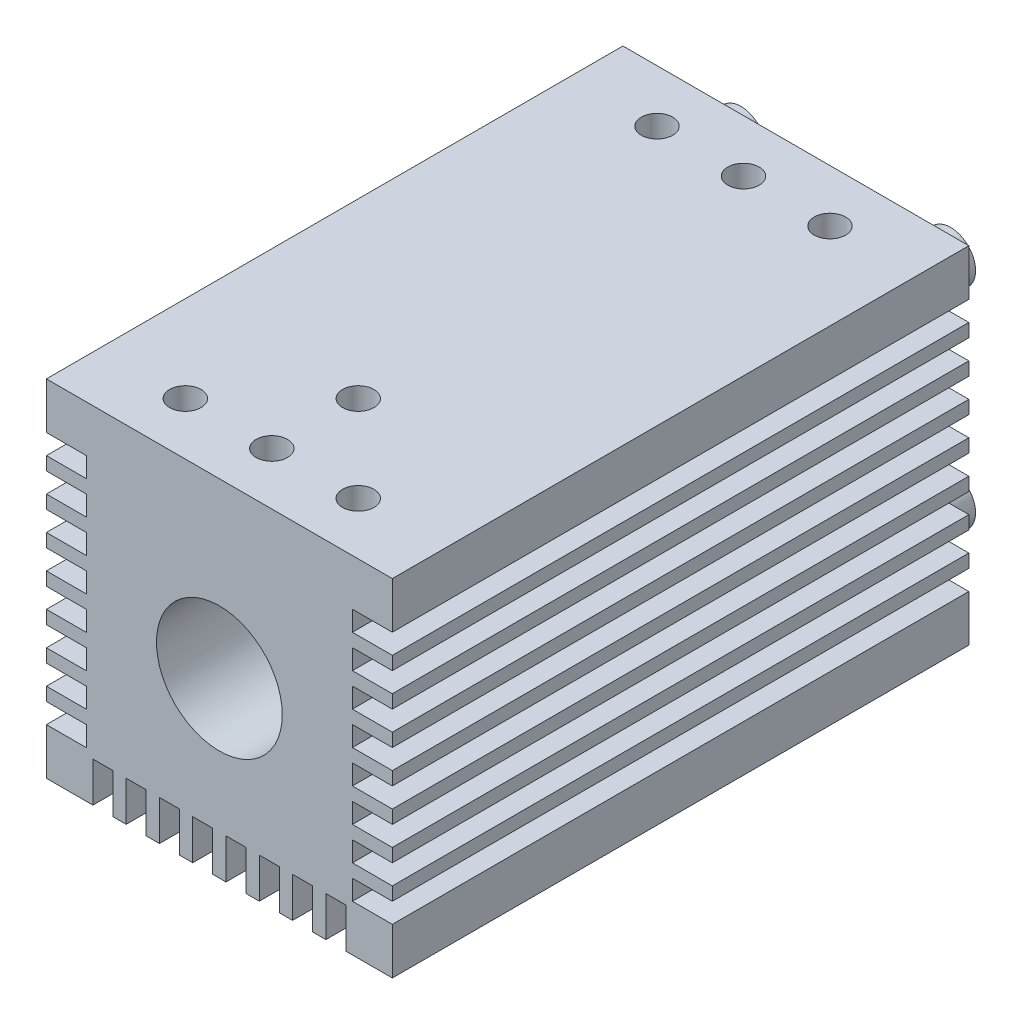
SolidWorks part; units mm, degrees
ref_plane "Front (1)" through (0, 0, 0) normal (0, 0, 1) x (1, 0, 0)
ref_plane "Top (2)" through (0, 0, 0) normal (0, 1, 0) x (1, 0, 0)
ref_plane "Right (3)" through (0, 0, 0) normal (1, 0, 0) x (0, 0, -1)
ref_axis "X-Axis" through (-80.9, 0, 0) along (1, 0, 0)
ref_axis "Y-Axis" through (0, -50, 0) along (0, 1, 0)
ref_axis "Z-Axis" through (0, 0, 50) along (0, 0, -1)
sketch "Sketch1" plane through (0, 0, 0) normal (0, 0, 1) x (1, 0, 0)
  line L0 (0, 0) -> (16.5, 16.5) construction
  line L1 (0, 0) -> (33, 0)
  line L2 (0, 0) -> (0, 33)
  line L3 (0, 33) -> (33, 33)
  line L4 (33, 0) -> (33, 33)
  line L5 (16.5, 16.5) -> (33, 33) construction
  circle A0 centre (16.5, 16.5) radius 6
  dimension "D3" = 12
  dimension "D1" = 33
  dimension "D2" = 33
extrude "Boss-Extrude1" add sketch "Sketch1" against normal blind 55
sketch "Sketch2" plane through (0, 33, 0) normal (0, 1, 0) x (1, 0, 0)
  line L0 (0, 5) -> (8.25, 5) construction
  line L1 (0, 55) -> (0, 0) construction
  line L2 (8.25, 5) -> (16.5, 5) construction
  line L3 (16.5, 5) -> (24.75, 5) construction
  line L4 (24.75, 5) -> (33, 5) construction
  line L5 (33, 55) -> (33, 0) construction
  line L6 (16.5, 13.25) -> (16.5, 5) construction
  line L7 (16.5, 5) -> (16.5, 0) construction
  line L8 (33, 0) -> (0, 0) construction
  line L9 (0, 50) -> (8.25, 50) construction
  line L10 (8.25, 50) -> (16.5, 50) construction
  line L11 (16.5, 50) -> (24.75, 50) construction
  line L12 (24.75, 50) -> (33, 50) construction
  line L13 (33, 55) -> (0, 55) construction
  circle A0 centre (8.25, 5) radius 1.5
  circle A1 centre (16.5, 5) radius 1.5
  circle A2 centre (24.75, 5) radius 1.5
  circle A3 centre (8.25, 50) radius 1.5
  circle A4 centre (16.5, 50) radius 1.5
  circle A5 centre (24.75, 50) radius 1.5
  circle A6 centre (16.5, 13.25) radius 1.5
  dimension "D3" = 3
  dimension "D1" = 5
  dimension "D2" = 5
extrude "Cut-Extrude1" cut sketch "Sketch2" against normal blind 12.7
sketch "Sketch5" plane through (0, 0, 0) normal (0, 0, 1) x (1, 0, 0)
  line L0 (0, 4.435) -> (3.81, 4.435)
  line L1 (0, 33) -> (0, 0) construction
  line L2 (3.81, 4.435) -> (3.81, 6.34)
  line L3 (3.81, 6.34) -> (0, 6.34)
  line L4 (0, 6.34) -> (0, 7.61)
  line L5 (0, 7.61) -> (3.81, 7.61)
  line L6 (3.81, 7.61) -> (3.81, 9.515)
  line L7 (3.81, 9.515) -> (0, 9.515)
  line L8 (0, 9.515) -> (0, 10.785)
  line L9 (0, 10.785) -> (3.81, 10.785)
  line L10 (3.81, 10.785) -> (3.81, 12.69)
  line L11 (3.81, 12.69) -> (0, 12.69)
  line L12 (0, 12.69) -> (0, 13.96)
  line L13 (0, 13.96) -> (3.81, 13.96)
  line L14 (3.81, 13.96) -> (3.81, 15.865)
  line L15 (3.81, 15.865) -> (0, 15.865)
  line L16 (0, 15.865) -> (0, 17.135)
  line L17 (0, 17.135) -> (3.81, 17.135)
  line L18 (3.81, 17.135) -> (3.81, 19.04)
  line L19 (3.81, 19.04) -> (0, 19.04)
  line L20 (0, 19.04) -> (0, 20.31)
  line L21 (0, 20.31) -> (3.81, 20.31)
  line L22 (3.81, 20.31) -> (3.81, 22.215)
  line L23 (3.81, 22.215) -> (0, 22.215)
  line L24 (0, 22.215) -> (0, 23.485)
  line L25 (0, 23.485) -> (3.81, 23.485)
  line L26 (3.81, 23.485) -> (3.81, 25.39)
  line L27 (3.81, 25.39) -> (0, 25.39)
  line L28 (0, 25.39) -> (0, 26.66)
  line L29 (0, 26.66) -> (3.81, 26.66)
  line L30 (3.81, 26.66) -> (3.81, 28.565)
  line L31 (3.81, 28.565) -> (0, 28.565)
  line L32 (0, 28.565) -> (0, 4.435)
  line L34 (4.435, 33) -> (4.435, 29.19) [skipped]
  line L35 (4.435, 29.19) -> (6.34, 29.19) [skipped]
  line L36 (6.34, 29.19) -> (6.34, 33) [skipped]
  line L37 (6.34, 33) -> (7.61, 33) [skipped]
  line L38 (7.61, 33) -> (7.61, 29.19) [skipped]
  line L39 (7.61, 29.19) -> (9.515, 29.19) [skipped]
  line L40 (9.515, 29.19) -> (9.515, 33) [skipped]
  line L41 (9.515, 33) -> (10.785, 33) [skipped]
  line L42 (10.785, 33) -> (10.785, 29.19) [skipped]
  line L43 (10.785, 29.19) -> (12.69, 29.19) [skipped]
  line L44 (12.69, 29.19) -> (12.69, 33) [skipped]
  line L45 (12.69, 33) -> (13.96, 33) [skipped]
  line L46 (13.96, 33) -> (13.96, 29.19) [skipped]
  line L47 (13.96, 29.19) -> (15.865, 29.19) [skipped]
  line L48 (15.865, 29.19) -> (15.865, 33) [skipped]
  line L49 (15.865, 33) -> (17.135, 33) [skipped]
  line L50 (17.135, 33) -> (17.135, 29.19) [skipped]
  line L51 (17.135, 29.19) -> (19.04, 29.19) [skipped]
  line L52 (19.04, 29.19) -> (19.04, 33) [skipped]
  line L53 (19.04, 33) -> (20.31, 33) [skipped]
  line L54 (20.31, 33) -> (20.31, 29.19) [skipped]
  line L55 (20.31, 29.19) -> (22.215, 29.19) [skipped]
  line L56 (22.215, 29.19) -> (22.215, 33) [skipped]
  line L57 (22.215, 33) -> (23.485, 33) [skipped]
  line L58 (23.485, 33) -> (23.485, 29.19) [skipped]
  line L59 (23.485, 29.19) -> (25.39, 29.19) [skipped]
  line L60 (25.39, 29.19) -> (25.39, 33) [skipped]
  line L61 (25.39, 33) -> (26.66, 33) [skipped]
  line L62 (26.66, 33) -> (26.66, 29.19) [skipped]
  line L63 (26.66, 29.19) -> (28.565, 29.19) [skipped]
  line L64 (28.565, 29.19) -> (28.565, 33) [skipped]
  line L65 (28.565, 33) -> (4.435, 33) [skipped]
  line L67 (33, 28.565) -> (29.19, 28.565)
  line L68 (29.19, 28.565) -> (29.19, 26.66)
  line L69 (29.19, 26.66) -> (33, 26.66)
  line L70 (33, 26.66) -> (33, 25.39)
  line L71 (33, 25.39) -> (29.19, 25.39)
  line L72 (29.19, 25.39) -> (29.19, 23.485)
  line L73 (29.19, 23.485) -> (33, 23.485)
  line L74 (33, 23.485) -> (33, 22.215)
  line L75 (33, 22.215) -> (29.19, 22.215)
  line L76 (29.19, 22.215) -> (29.19, 20.31)
  line L77 (29.19, 20.31) -> (33, 20.31)
  line L78 (33, 20.31) -> (33, 19.04)
  line L79 (33, 19.04) -> (29.19, 19.04)
  line L80 (29.19, 19.04) -> (29.19, 17.135)
  line L81 (29.19, 17.135) -> (33, 17.135)
  line L82 (33, 17.135) -> (33, 15.865)
  line L83 (33, 15.865) -> (29.19, 15.865)
  line L84 (29.19, 15.865) -> (29.19, 13.96)
  line L85 (29.19, 13.96) -> (33, 13.96)
  line L86 (33, 13.96) -> (33, 12.69)
  line L87 (33, 12.69) -> (29.19, 12.69)
  line L88 (29.19, 12.69) -> (29.19, 10.785)
  line L89 (29.19, 10.785) -> (33, 10.785)
  line L90 (33, 10.785) -> (33, 9.515)
  line L91 (33, 9.515) -> (29.19, 9.515)
  line L92 (29.19, 9.515) -> (29.19, 7.61)
  line L93 (29.19, 7.61) -> (33, 7.61)
  line L94 (33, 7.61) -> (33, 6.34)
  line L95 (33, 6.34) -> (29.19, 6.34)
  line L96 (29.19, 6.34) -> (29.19, 4.435)
  line L97 (29.19, 4.435) -> (33, 4.435)
  line L98 (33, 4.435) -> (33, 28.565)
  line L100 (28.565, 0) -> (28.565, 3.81)
  line L101 (28.565, 3.81) -> (26.66, 3.81)
  line L102 (26.66, 3.81) -> (26.66, 0)
  line L103 (26.66, 0) -> (25.39, 0)
  line L104 (25.39, 0) -> (25.39, 3.81)
  line L105 (25.39, 3.81) -> (23.485, 3.81)
  line L106 (23.485, 3.81) -> (23.485, 0)
  line L107 (23.485, 0) -> (22.215, 0)
  line L108 (22.215, 0) -> (22.215, 3.81)
  line L109 (22.215, 3.81) -> (20.31, 3.81)
  line L110 (20.31, 3.81) -> (20.31, 0)
  line L111 (20.31, 0) -> (19.04, 0)
  line L112 (19.04, 0) -> (19.04, 3.81)
  line L113 (19.04, 3.81) -> (17.135, 3.81)
  line L114 (17.135, 3.81) -> (17.135, 0)
  line L115 (17.135, 0) -> (15.865, 0)
  line L116 (15.865, 0) -> (15.865, 3.81)
  line L117 (15.865, 3.81) -> (13.96, 3.81)
  line L118 (13.96, 3.81) -> (13.96, 0)
  line L119 (13.96, 0) -> (12.69, 0)
  line L120 (12.69, 0) -> (12.69, 3.81)
  line L121 (12.69, 3.81) -> (10.785, 3.81)
  line L122 (10.785, 3.81) -> (10.785, 0)
  line L123 (10.785, 0) -> (9.515, 0)
  line L124 (9.515, 0) -> (9.515, 3.81)
  line L125 (9.515, 3.81) -> (7.61, 3.81)
  line L126 (7.61, 3.81) -> (7.61, 0)
  line L127 (7.61, 0) -> (6.34, 0)
  line L128 (6.34, 0) -> (6.34, 3.81)
  line L129 (6.34, 3.81) -> (4.435, 3.81)
  line L130 (4.435, 3.81) -> (4.435, 0)
  line L131 (4.435, 0) -> (28.565, 0)
  line L133 (0, 0) -> (33, 0) construction
  line L134 (33, 0) -> (33, 33) construction
  point P32 (0, 16.5)
  point P138 (16.5, 16.5)
  line M20 (0, 33) -> (0, 0)
  line M21 (0, 0) -> (33, 0)
  line M22 (33, 0) -> (33, 33)
  dimension "D1" = 1.905
  dimension "D2" = 1.27
  dimension "D3" = 3.81
  dimension "D4" = 4
extrude "Cut-Extrude2" cut sketch "Sketch5" against normal through all contours L30 L31 L29 M20 | L26 L27 L25 M20 | L22 L23 L21 M20 | L18 L19 L17 M20 | L14 L15 L13 M20 | L10 L11 L9 M20 | L6 L7 L5 M20 | L2 L3 L0 M20 | L129 L130 L128 M21 | L125 L126 L124 M21 | L121 L122 L120 M21 | L117 L118 L116 M21 | L113 L114 L112 M21 | L109 L110 L108 M21 | L105 L106 L104 M21 | L101 L102 L100 M21 | L96 L97 L95 M22 | L92 L93 L91 M22 | L88 L89 L87 M22 | L84 L85 L83 M22 | L80 L81 L79 M22 | L76 L77 L75 M22 | L72 L73 L71 M22 | L68 L69 L67 M22 region at (1.905, 5.3875, 0) region at (1.905, 27.6125, 0) region at (1.905, 24.4375, 0) region at (1.905, 21.2625, 0) region at (1.905, 18.0875, 0) region at (1.905, 14.9125, 0) region at (1.905, 11.7375, 0) region at (1.905, 8.5625, 0) region at (31.095, 27.6125, 0) region at (31.095, 24.4375, 0) region at (31.095, 21.2625, 0) region at (31.095, 18.0875, 0) region at (31.095, 14.9125, 0) region at (31.095, 11.7375, 0) region at (31.095, 8.5625, 0) region at (31.095, 5.3875, 0) region at (27.6125, 1.905, 0) region at (24.4375, 1.905, 0) region at (21.2625, 1.905, 0) region at (18.0875, 1.905, 0) region at (14.9125, 1.905, 0) region at (11.7375, 1.905, 0) region at (8.5625, 1.905, 0) region at (5.3875, 1.905, 0)
sketch "Sketch3" plane through (0, 0, -55) normal (0, 0, 1) x (1, 0, 0)
  line L1 (6.5, 26.5) -> (26.5, 26.5) construction
  line L2 (26.5, 26.5) -> (26.5, 6.5) construction
  line L3 (26.5, 6.5) -> (6.5, 6.5) construction
  line L4 (6.5, 6.5) -> (6.5, 26.5) construction
  line L9 (16.5, 26.5) -> (16.5, 16.5) construction
  circle A0 centre (6.5, 26.5) radius 2.3813
  circle A1 centre (26.5, 26.5) radius 2.3813
  circle A2 centre (26.5, 6.5) radius 2.3813
  circle A3 centre (6.5, 6.5) radius 2.3813
  point P10 (26.5, 16.5)
  dimension "D1" = 4.7625
  dimension "D2" = 20
extrude "Boss-Extrude2" add sketch "Sketch3" against normal blind 4.7625
